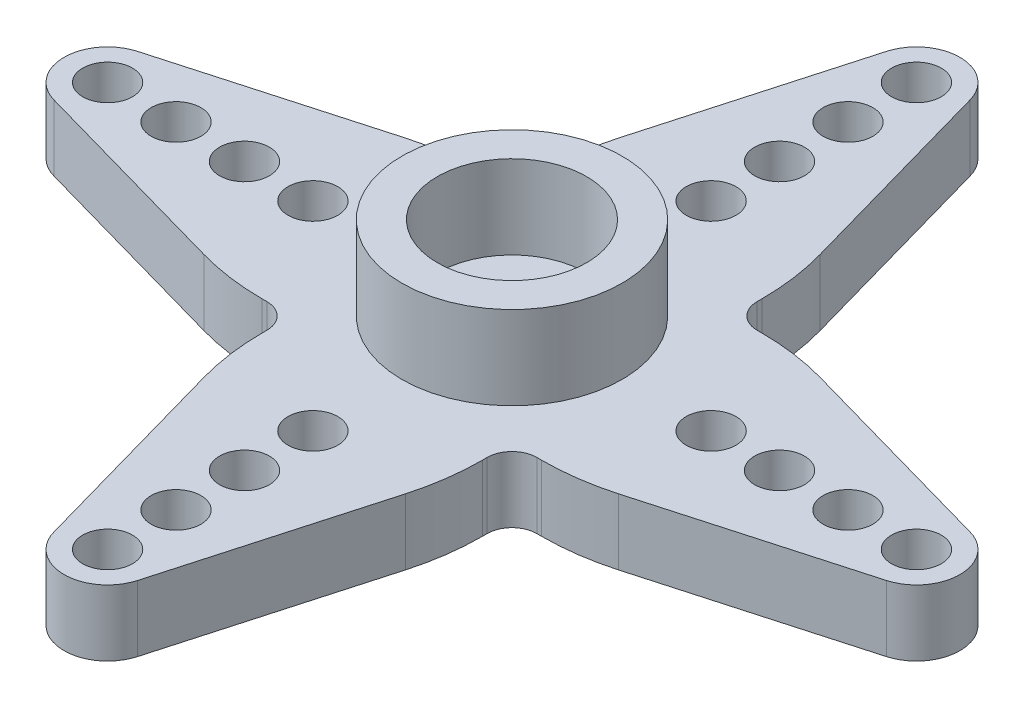
SolidWorks part; units mm, degrees
ref_plane "Front Plane" through (0, 0, 0) normal (0, 0, 1) x (1, 0, 0)
ref_plane "Top Plane" through (0, 0, 0) normal (0, 1, 0) x (1, 0, 0)
ref_plane "Right Plane" through (0, 0, 0) normal (1, 0, 0) x (0, 0, -1)
sketch "Sketch1" plane through (0, 0, 0) normal (0, 1, 0) x (1, 0, 0)
  line L0 (-30.4576, -32.4711) -> (-30.6505, -32.4711)
  line L1 (-44.4058, -32.846) -> (-52.8002, -35.2117)
  line L2 (-52.8002, -38.5805) -> (-44.4058, -40.9461)
  line L3 (-41.6933, -41.3211) -> (-41.5005, -41.3211)
  line L4 (-52.3255, -36.8961) -> (-19.8255, -36.8961) construction
  line L5 (-36.0755, -32.4711) -> (-36.0755, -41.3211) construction
  line L6 (-19.3508, -38.5805) -> (-27.7451, -40.9461)
  line L7 (-27.7451, -32.846) -> (-19.3508, -35.2117)
  line L8 (-34.3911, -20.1714) -> (-32.0254, -28.5657)
  line L9 (-31.6505, -31.2782) -> (-31.6505, -31.4711)
  line L10 (-40.5005, -42.5139) -> (-40.5005, -42.3211)
  line L11 (-40.1255, -28.5657) -> (-37.7598, -20.1714)
  line L12 (-40.1255, -45.2264) -> (-37.7598, -53.6208)
  line L13 (-34.3911, -53.6208) -> (-32.0254, -45.2264)
  line L14 (-40.5005, -31.4711) -> (-40.5005, -31.2782)
  line L15 (-41.5005, -32.4711) -> (-41.6933, -32.4711)
  line L16 (-31.6505, -42.3211) -> (-31.6505, -42.5139)
  line L17 (-30.6505, -41.3211) -> (-30.4576, -41.3211)
  circle A0 centre (-36.0755, -36.8961) radius 3
  circle A1 centre (-36.0755, -36.8961) radius 4.425
  arc A2 (-52.8002, -35.2117) -> (-52.8002, -38.5805) centre (-52.3255, -36.8961) ccw
  arc A3 (-41.6933, -32.4711) -> (-44.4058, -32.846) centre (-41.6933, -42.4711) ccw
  arc A4 (-41.6933, -41.3211) -> (-44.4058, -40.9461) centre (-41.6933, -31.3211) cw
  circle A5 centre (-52.3255, -36.8961) radius 1
  circle A6 centre (-49.5755, -36.8961) radius 1
  circle A7 centre (-46.8255, -36.8961) radius 1
  circle A8 centre (-44.0755, -36.8961) radius 1
  circle A9 centre (-28.0755, -36.8961) radius 1
  circle A10 centre (-25.3255, -36.8961) radius 1
  circle A11 centre (-22.5755, -36.8961) radius 1
  circle A12 centre (-19.8255, -36.8961) radius 1
  arc A13 (-30.4576, -41.3211) -> (-27.7451, -40.9461) centre (-30.4576, -31.3211) ccw
  arc A14 (-30.4576, -32.4711) -> (-27.7451, -32.846) centre (-30.4576, -42.4711) cw
  arc A15 (-19.3508, -35.2117) -> (-19.3508, -38.5805) centre (-19.8255, -36.8961) cw
  arc A16 (-34.3911, -20.1714) -> (-37.7598, -20.1714) centre (-36.0755, -20.6461) ccw
  arc A17 (-40.5005, -31.2782) -> (-40.1255, -28.5657) centre (-30.5005, -31.2782) cw
  arc A18 (-32.0254, -28.5657) -> (-31.6505, -31.2782) centre (-41.6505, -31.2782) cw
  circle A19 centre (-36.0755, -20.6461) radius 1
  circle A20 centre (-36.0755, -23.3961) radius 1
  circle A21 centre (-36.0755, -26.1461) radius 1
  circle A22 centre (-36.0755, -28.8961) radius 1
  circle A23 centre (-36.0755, -44.8961) radius 1
  circle A24 centre (-36.0755, -47.6461) radius 1
  circle A25 centre (-36.0755, -50.3961) radius 1
  circle A26 centre (-36.0755, -53.1461) radius 1
  arc A27 (-32.0254, -45.2264) -> (-31.6505, -42.5139) centre (-41.6505, -42.5139) ccw
  arc A28 (-40.5005, -42.5139) -> (-40.1255, -45.2264) centre (-30.5005, -42.5139) ccw
  arc A29 (-34.3911, -53.6208) -> (-37.7598, -53.6208) centre (-36.0755, -53.1461) cw
  arc A30 (-41.5005, -41.3211) -> (-40.5005, -42.3211) centre (-41.5005, -42.3211) cw
  arc A31 (-31.6505, -42.3211) -> (-30.6505, -41.3211) centre (-30.6505, -42.3211) cw
  arc A32 (-30.6505, -32.4711) -> (-31.6505, -31.4711) centre (-30.6505, -31.4711) cw
  arc A33 (-40.5005, -31.4711) -> (-41.5005, -32.4711) centre (-41.5005, -31.4711) cw
  point P13 (-43.0755, -32.4711)
  point P39 (-29.0755, -32.4711)
  point P50 (-40.5005, -29.8961)
  point P54 (-40.5005, -36.8961)
  point P61 (-31.6505, -36.8961)
  point P75 (-40.5005, -43.8961)
  point P84 (-31.6505, -41.3211)
  point P89 (-40.5005, -32.4711)
  dimension "D1" = 6
  dimension "D2" = 8.85
  dimension "D7" = 3.5
  dimension "D5" = 10
  dimension "D6" = 10
  dimension "D8" = 2
  dimension "D10" = 3.5
  dimension "D13" = 10
  dimension "D14" = 10
  dimension "D15" = 2
  dimension "D16" = 1
  dimension "D3" = 7
  dimension "D4" = 16.25
  dimension "D11" = 16.25
  dimension "D12" = 7
  dimension "D9" = 4
extrude "Boss-Extrude1" add sketch "Sketch1" along normal blind 2.65 contours L14 A33 L15 A3 L1 A2 L2 A4 L3 A30 L10 A28 L12 A29 L13 A27 L16 A31 L17 A13 L6 A15 L7 A14 L0 A32 L9 A18 L8 A16 L11 A17 A26 A24 A12 A10 A1 A5 A6 A7 A8 | A0 region at (-29.1582, 0, 33.0696) region at (-36.0755, 0, 36.8961)
extrude "Boss-Extrude2" add sketch "Sketch1<4>" along normal blind 6 contours A1 A0 region at (-40.3753, 0, 36.8961)
sketch "Sketch1<4>" plane through (0, 0, 0) normal (0, 1, 0) x (1, 0, 0) same geometry as "Sketch1"
sketch "Sketch2" plane through (0, 0, 0) normal (0, -1, 0) x (1, 0, 0)
  circle A0 centre (-36.0755, 36.8961) radius 3.5
  circle A1 centre (-36.0755, 36.8961) radius 3.25
  circle A2 centre (-36.0755, 36.8961) radius 1.75
  circle A3 centre (-36.0755, 36.8961) radius 4.5
  circle M49 centre (-36.0755, 36.8961) radius 3
  dimension "D1" = 7
  dimension "D2" = 6.5
  dimension "D3" = 3.5
  dimension "D4" = 9
extrude "Cut-Extrude1" cut sketch "Sketch2" against normal blind 0.2 contours A3 A0 | A1 M49 | A2 M49 region at (-39.2335, 0, 36.8961) region at (-40.4482, 0, 36.8961) region at (-38.9906, 0, 36.8961)
extrude "Boss-Extrude3" add sketch "Sketch2<4>" along normal blind 0.5 contours A0 A1 region at (-39.4765, 0, 36.8961)
sketch "Sketch2<4>" plane through (0, 0, 0) normal (0, -1, 0) x (1, 0, 0) same geometry as "Sketch2"
extrude "Cut-Extrude2" cut sketch "Sketch2<5>" against normal up to next contours A2 region at (-36.0755, 0, 36.8961)
sketch "Sketch2<5>" plane through (0, 0, 0) normal (0, -1, 0) x (1, 0, 0) same geometry as "Sketch2"
